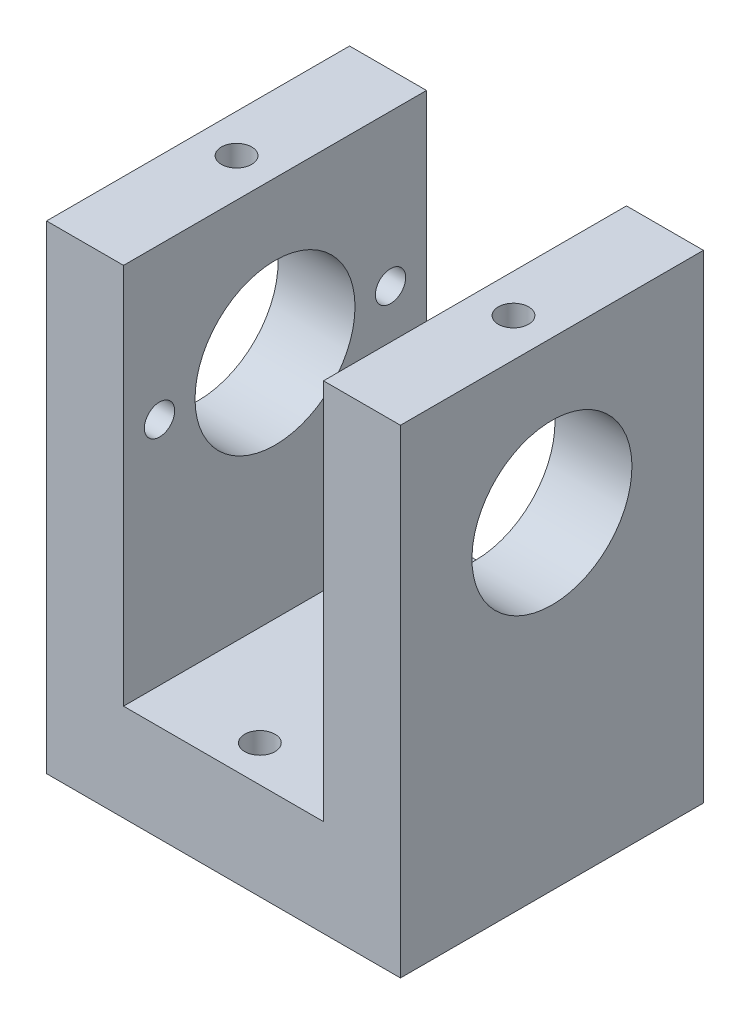
SolidWorks part; units mm, degrees
material "6061 Alloy"
ref_plane "Front Plane" through (0, 0, 0) normal (0, 0, 1) x (1, 0, 0)
ref_plane "Top Plane" through (0, 0, 0) normal (0, 1, 0) x (1, 0, 0)
ref_plane "Right Plane" through (0, 0, 0) normal (1, 0, 0) x (0, 0, -1)
sketch "Sketch1" plane through (0, 0, 0) normal (0, 0, 1) x (1, 0, 0)
  line L0 (-14.6, 12.5) -> (-14.6, -27)
  line L1 (-14.6, -27) -> (14.6, -27)
  line L2 (14.6, -27) -> (14.6, 12.5)
  line L3 (-8.25, 12.5) -> (-8.25, -19)
  line L4 (-8.25, -19) -> (8.25, -19)
  line L5 (8.25, -19) -> (8.25, 12.5)
  line L6 (-14.6, 12.5) -> (-8.25, 12.5)
  line L7 (8.25, 12.5) -> (14.6, 12.5)
  line L8 (0, -19) -> (0, -27) construction
  line L9 (14.6, -27) -> (14.6, 28.7745) construction
  dimension "D1" = 8
  dimension "D2" = 0
  dimension "D3" = 29.2
  dimension "D4" = 39.5
  dimension "D5" = 39.5
  dimension "D6" = 27
  dimension "D7" = 6.35
extrude "Boss-Extrude1" add sketch "Sketch1" along normal blind 12.5 and the other way blind 12.5
sketch "Sketch3" plane through (-14.6, 0, 0) normal (-1, 0, 0) x (0, 0, 1)
  circle A0 centre (0, 0) radius 6.6
  dimension "D3" = 13.2
extrude "Cut-Extrude1" cut sketch "Sketch3" against normal through all
hole_wizard "Tap Drill for M3x0.5 Tap3" positions "Sketch12" profile "Sketch13" hole size "M3x0.5" standard "ANSI Metric"
sketch "Sketch12" plane through (0, 12.5, 0) normal (0, 1, 0) x (1, 0, 0)
  line L0 (-14.6, 12.5) -> (-14.6, -12.5) construction
  line L1 (-8.25, 12.5) -> (-14.6, 12.5) construction
  line L2 (14.6, 12.5) -> (8.25, 12.5) construction
  line L3 (14.6, 12.5) -> (14.6, -12.5) construction
  point P0 (-11.425, 0)
  point P2 (11.425, 0)
  dimension "D1" = 3.175
  dimension "D2" = 12.5
  dimension "D3" = 12.5
  dimension "D4" = 3.175
sketch "Sketch13" plane through (-11.425, 12.5, 0) normal (1, 0, 0) x (0, 0, 1)
  line L0 (0, 0) -> (0, 7.7511)
  line L1 (0, 7.7511) -> (1.25, 7)
  line L2 (1.25, 7) -> (1.25, 0)
  line L5 (1.25, 0) -> (0, 0)
  line L10 (0, 7.7511) -> (-1.25, 7) construction
  line L11 (0, -6.35) -> (0, 107.95) construction
  dimension "Hole Dia." = 2.5
  dimension "Hole Depth" = 7
  dimension "Drill Angle" = 118
hole_wizard "Tap Drill for M4x0.7 Tap1" positions "Sketch15" profile "Sketch16" hole size "M4x0.7" standard "ANSI Metric"
sketch "Sketch15" plane through (0, -27, 0) normal (0, -1, 0) x (-1, 0, 0)
  line L0 (-14.6, 12.5) -> (-14.6, -12.5) construction
  line L1 (14.6, 12.5) -> (14.6, -12.5) construction
  point P0 (-10.1, 0)
  point P2 (10.1, 0)
  dimension "D1" = 4.5
  dimension "D2" = 4.5
sketch "Sketch16" plane through (10.1, -27, 0) normal (1, 0, 0) x (0, 0, -1)
  line L0 (0, 0) -> (0, 8.9914)
  line L1 (0, 8.9914) -> (1.65, 8)
  line L2 (1.65, 8) -> (1.65, 0)
  line L5 (1.65, 0) -> (0, 0)
  line L10 (0, 8.9914) -> (-1.65, 8) construction
  line L11 (0, -6.35) -> (0, 107.95) construction
  dimension "Hole Dia." = 3.3
  dimension "Hole Depth" = 8
  dimension "Drill Angle" = 118
hole_wizard "Tap Drill for M3x0.5 Tap4" positions "Sketch17" profile "Sketch19" hole size "M3x0.5" standard "ANSI Metric" end condition up to next
sketch "Sketch17" plane through (-14.6, 0, 0) normal (-1, 0, 0) x (0, 0, 1)
  line L0 (-12.5, 12.5) -> (-12.5, -27) construction
  line L1 (12.5, 12.5) -> (12.5, -27) construction
  point P0 (-9.53, 0)
  point P2 (9.53, 0)
  dimension "D1" = 2.97
  dimension "D2" = 2.97
sketch "Sketch19" plane through (-14.6, 0, -9.53) normal (0, 1, 0) x (0, 0, 1)
  line L0 (0, 0) -> (0, 6.35)
  line L1 (0, 6.35) -> (1.25, 6.35)
  line L2 (1.25, 6.35) -> (1.25, 0)
  line L5 (1.25, 0) -> (0, 0)
  line L11 (0, -6.35) -> (0, 107.95) construction
  dimension "Thru Hole Dia." = 2.5
  dimension "Thru Hole Depth" = 6.35
hole_wizard "Tap Drill for M3x0.5 Tap5" positions "Sketch21" profile "Sketch22" hole size "M3x0.5" standard "ANSI Metric" end condition up to next
sketch "Sketch21" plane through (0, -27, 0) normal (0, -1, 0) x (-1, 0, 0)
  line L0 (14.6, -12.5) -> (-14.6, -12.5) construction
  point P0 (0, -9.5)
  point P2 (0, 9.5)
  dimension "D1" = 19
  dimension "D2" = 3
sketch "Sketch22" plane through (0, -27, 9.5) normal (1, 0, 0) x (0, 0, -1)
  line L0 (0, 0) -> (0, 8)
  line L1 (0, 8) -> (1.25, 8)
  line L2 (1.25, 8) -> (1.25, 0)
  line L5 (1.25, 0) -> (0, 0)
  line L11 (0, -6.35) -> (0, 107.95) construction
  dimension "Thru Hole Dia." = 2.5
  dimension "Thru Hole Depth" = 8
